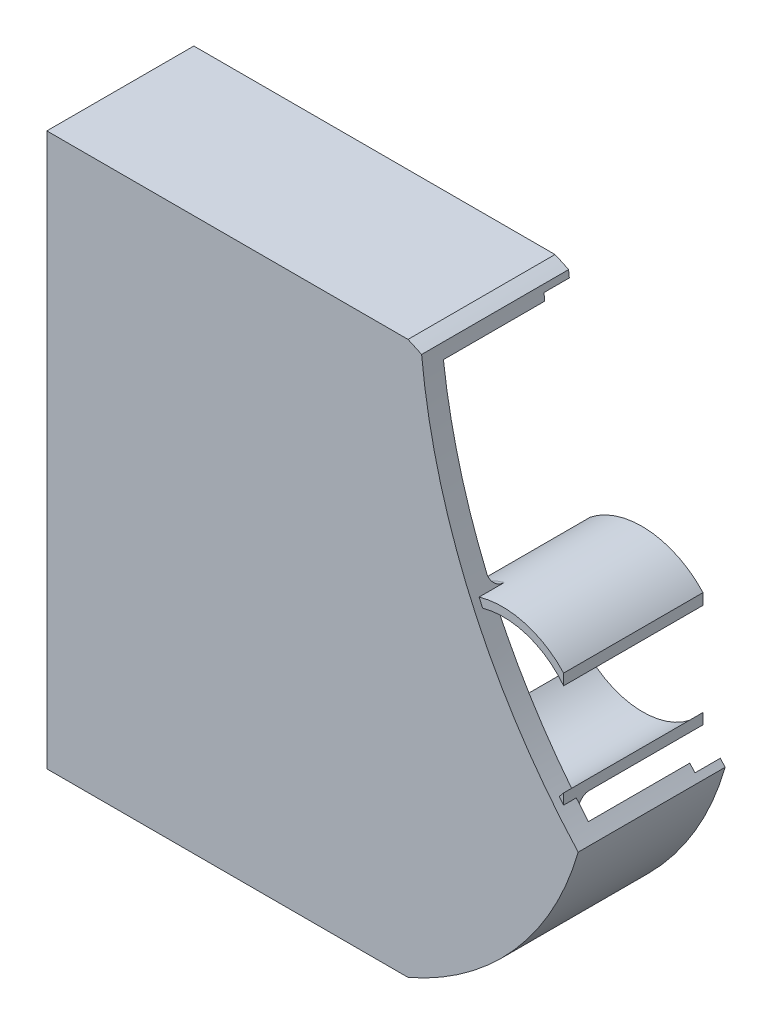
SolidWorks part; units mm, degrees
ref_plane "Front Plane" through (0, 0, 0) normal (0, 0, 1) x (1, 0, 0)
ref_plane "Top Plane" through (0, 0, 0) normal (0, 1, 0) x (1, 0, 0)
ref_plane "Right Plane" through (0, 0, 0) normal (1, 0, 0) x (0, 0, -1)
sketch "Sketch1" plane through (0, 0, 0) normal (0, 0, 1) x (1, 0, 0)
  line L1 (-74.2297, 45.7275) -> (-49.2297, 45.7275)
  line L2 (-74.2297, 45.7275) -> (-74.2297, 5.7275)
  line L3 (-74.2297, 5.7275) -> (-49.2297, 5.7275)
  line L4 (-49.2297, 45.7275) -> (-49.2297, 5.7275)
  dimension "D1" = 40
  dimension "D2" = 25
extrude "Boss-Extrude1" add sketch "Sketch1" along normal blind 8
sketch "Sketch2" plane through (0, 0, 0) normal (0, 0, 1) x (1, 0, 0)
  line L0 (-77.8888, 47.5275) -> (-77.8888, 3.9275)
  line L5 (-61.7297, 45.7275) -> (-61.7297, 25.7275)
  line L6 (-49.2297, 45.7275) -> (-74.2297, 45.7275) construction
  line L8 (-77.8888, 47.5275) -> (-49.3888, 47.5275)
  line L10 (-77.8888, 3.9275) -> (-49.3888, 3.9275)
  circle A1 centre (0.0074, 51.8244) radius 48.5612
  arc A3 (-49.3888, 47.5275) -> (-49.3888, 3.9275) centre (-58.7867, 25.7275) cw
  dimension "D6" = 43.6
  dimension "D8" = 28.5
  dimension "D9" = 28.5
extrude "Boss-Extrude5" add sketch "Sketch2" along normal blind 10.6 and the other way blind 1 contours L8 L0 region at (-60.1347, 24.8744, 0)
sketch "Sketch8" plane through (0, 0, 0) normal (0, 0, 1) x (1, 0, 0)
  line L0 (-76.8888, 46.5275) -> (-76.8888, 4.9275)
  line L1 (-76.8888, 4.9275) -> (-49.3888, 4.9275)
  line L2 (-76.8888, 46.5275) -> (-49.3888, 46.5275)
  line L3 (-77.8888, 47.5275) -> (-77.8888, 3.9275) construction
  arc A0 (-49.3888, 4.9275) -> (-49.3888, 46.5275) centre (-58.9321, 25.7275) ccw
  arc A2 (-48.3169, 47.0335) -> (-49.3888, 47.5275) centre (-58.7867, 25.7275) ccw construction
  point P8 (-36.0473, 25.7275)
  point P12 (-35.0473, 25.7275)
  dimension "D1" = 1
  dimension "D2" = 1
  dimension "D3" = 1
  dimension "D4" = 1
extrude "Cut-Extrude2" cut sketch "Sketch8" against normal blind 6 and the other way blind 9 contours A0 L2 L0 L1
sketch "Sketch9" plane through (0, 0, 0) normal (0, 0, 1) x (1, 0, 0)
  line L0 (-37.7093, 30.2625) -> (-37.7093, 29.3916)
  line L1 (-37.7093, 22.0742) -> (-37.7093, 21.228)
  line L2 (-46.6022, 30.9745) -> (-46.6022, 30.0766)
  line L3 (-46.6022, 21.3784) -> (-46.6022, 20.6468)
  arc A3 (-37.7093, 30.2625) -> (-46.6022, 30.9745) centre (-42.5385, 25.8379) ccw
  arc A4 (-37.7093, 21.228) -> (-46.6022, 20.6468) centre (-42.4688, 25.7275) cw
  arc A5 (-37.7093, 29.3916) -> (-46.6022, 30.0766) centre (-42.4641, 25.732) ccw
  arc A6 (-37.7093, 22.0742) -> (-46.6022, 21.3784) centre (-42.4688, 25.7275) cw
extrude "Boss-Extrude9" add sketch "Sketch9" along normal blind 10 and the other way blind 1
sketch "Sketch10" plane through (0, 0, 0) normal (0, 0, 1) x (1, 0, 0)
  line L0 (-76.8888, 47.0275) -> (-49.3888, 47.0275)
  line L1 (-49.3888, 46.5275) -> (-76.8888, 46.5275)
  line L2 (-76.8888, 47.0275) -> (-77.3888, 47.0275)
  line L3 (-77.3888, 47.0275) -> (-77.3888, 4.4275)
  line L4 (-77.3888, 4.4275) -> (-49.3888, 4.4275)
  line L5 (-76.8888, 46.5275) -> (-76.8888, 4.9275)
  line L6 (-76.8888, 4.9275) -> (-49.3888, 4.9275)
  arc A0 (-49.3888, 47.0275) -> (-49.3888, 4.4275) centre (-58.8322, 25.7275) cw
  arc A1 (-49.3888, 46.5275) -> (-49.3888, 4.9275) centre (-58.9321, 25.7275) cw
  dimension "D1" = 0.5
  dimension "D2" = 0.5
  dimension "D3" = 0.5
extrude "Cut-Extrude3" cut sketch "Sketch10" against normal blind 1 and the other way blind 1
fillet "Fillet8" radius 1 1 edges at (-45.5457, 31.6565, 9)
fillet "Fillet10" radius 1 1 edges at (-42.0417, 19.1918, 9)
